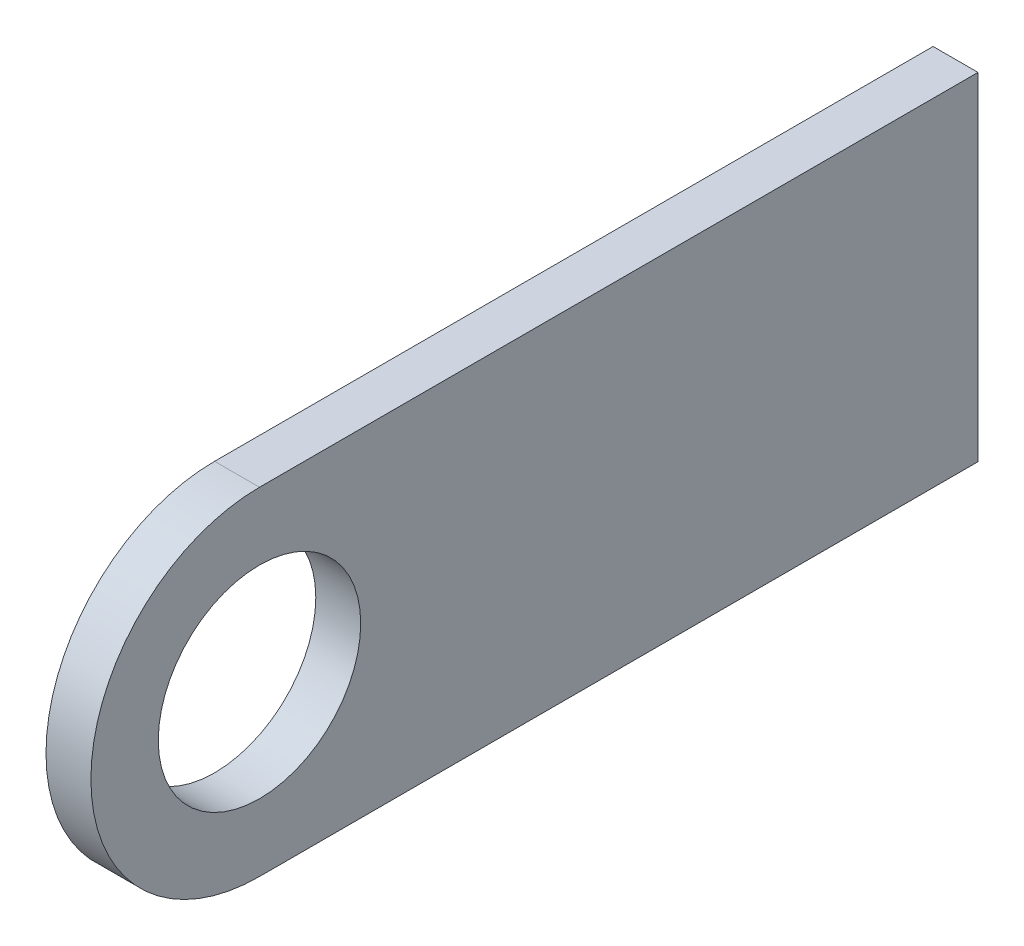
SolidWorks part; units mm, degrees
material "6061-T6 (SS)"
ref_plane "Front" through (0, 0, 0) normal (0, 0, 1) x (1, 0, 0)
ref_plane "Top" through (0, 0, 0) normal (0, 1, 0) x (1, 0, 0)
ref_plane "Right" through (0, 0, 0) normal (1, 0, 0) x (0, 0, -1)
sketch "Sketch1" plane through (0, 0, 0) normal (1, 0, 0) x (0, 0, -1)
  line L0 (0, -23.8379) -> (0, 23.8379)
  line L3 (0, 23.8379) -> (-101.6, 23.8379)
  line L4 (-101.6, -23.8379) -> (0, -23.8379)
  arc A0 (-101.6, 23.8379) -> (-101.6, -23.8379) centre (-101.6, 0) ccw
  circle A1 centre (-101.6, 0) radius 14.3129
  point P3 (0, 0)
  point P4 (0, 0)
  point P6 (0, 0)
  dimension "D3" = 28.6258
  dimension "D4" = 9.525
  dimension "D5" = 101.6
extrude "Boss-Extrude1" add sketch "Sketch1" along normal blind 6.35
